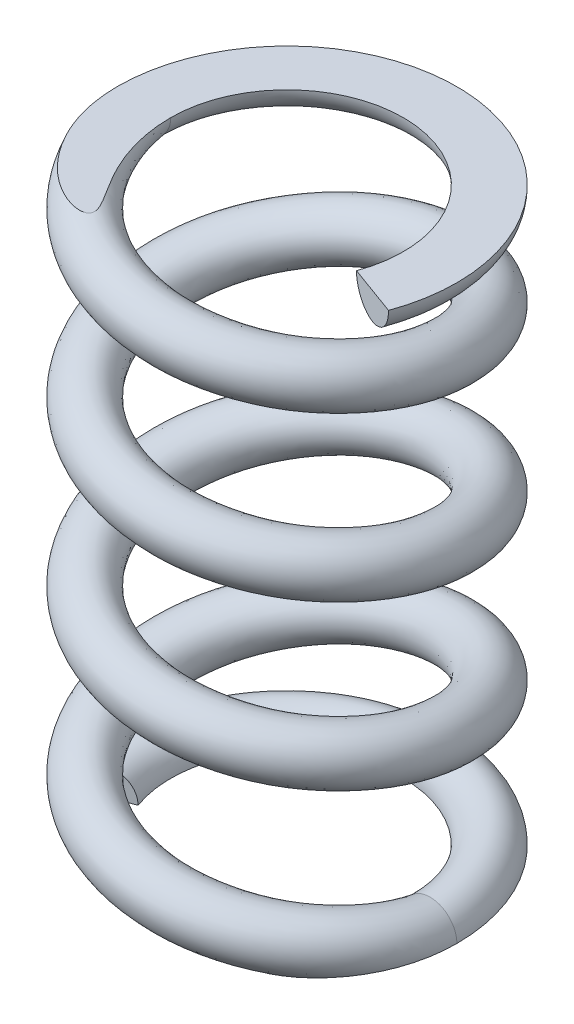
SolidWorks part; units mm, degrees
material "AISI 304"
ref_plane "Front Plane" through (0, 0, 0) normal (0, 0, 1) x (1, 0, 0)
ref_plane "Top Plane" through (0, 0, 0) normal (0, 1, 0) x (1, 0, 0)
ref_plane "Right Plane" through (0, 0, 0) normal (1, 0, 0) x (0, 0, -1)
sketch "Sketch1" plane through (0, 0, 0) normal (0, 0, 1) x (1, 0, 0)
  line L0 (0, 0) -> (2, 0) construction
  circle A0 centre (2, 0) radius 0.375
  point P7 (2, 0)
  dimension "D1" = 0.75
  dimension "D2" = 2
sketch "Sketch2" plane through (0, 0, 0) normal (0, 0, 1) x (1, 0, 0)
  line L0 (0, 0) -> (0, 8)
  dimension "D1" = 8
sketch "Sketch3" plane through (0, 0, 0) normal (0, 1, 0) x (1, 0, 0)
  circle A0 centre (0, 0) radius 2
curve "Helix/Spiral1" pitch 2.2857 height 8 radius 2 left hand yes centre (0, 0, 0) axis (0, 1, 0) start towards (1, 0, 0)
sweep "Sweep1" add profiles "Sketch1" path "Helix/Spiral1"
revolve "Revolve1" add sketch "Sketch1<3>" angle 200 about L0
sketch "Sketch1<3>" plane through (0, 0, 0) normal (0, 0, 1) x (1, 0, 0) same geometry as "Sketch1"
sketch "Sketch4" plane through (0, 0, 0) normal (0, 1, 0) x (1, 0, 0)
  circle A0 centre (0, 0) radius 2.5
  dimension "D1" = 5
extrude "Cut-Extrude1" cut sketch "Sketch4" against normal through all
sketch "Sketch6" plane through (0, 0, 0) normal (0, 0, -1) x (-1, 0, 0)
  circle A0 centre (2, 8) radius 0.375
  circle A1 centre (2, 8) radius 0.375 construction
revolve "Revolve2" add sketch "Sketch6" angle 200 about L0 reverse direction yes
ref_plane "Plane1" through (0, 8, 0) normal (0, 1, 0) x (1, 0, 0)
sketch "Sketch7" plane through (0, 8, 0) normal (0, 1, 0) x (1, 0, 0)
  circle A0 centre (0, 0) radius 2.5
  dimension "D1" = 5
extrude "Cut-Extrude2" cut sketch "Sketch7" along normal through all
